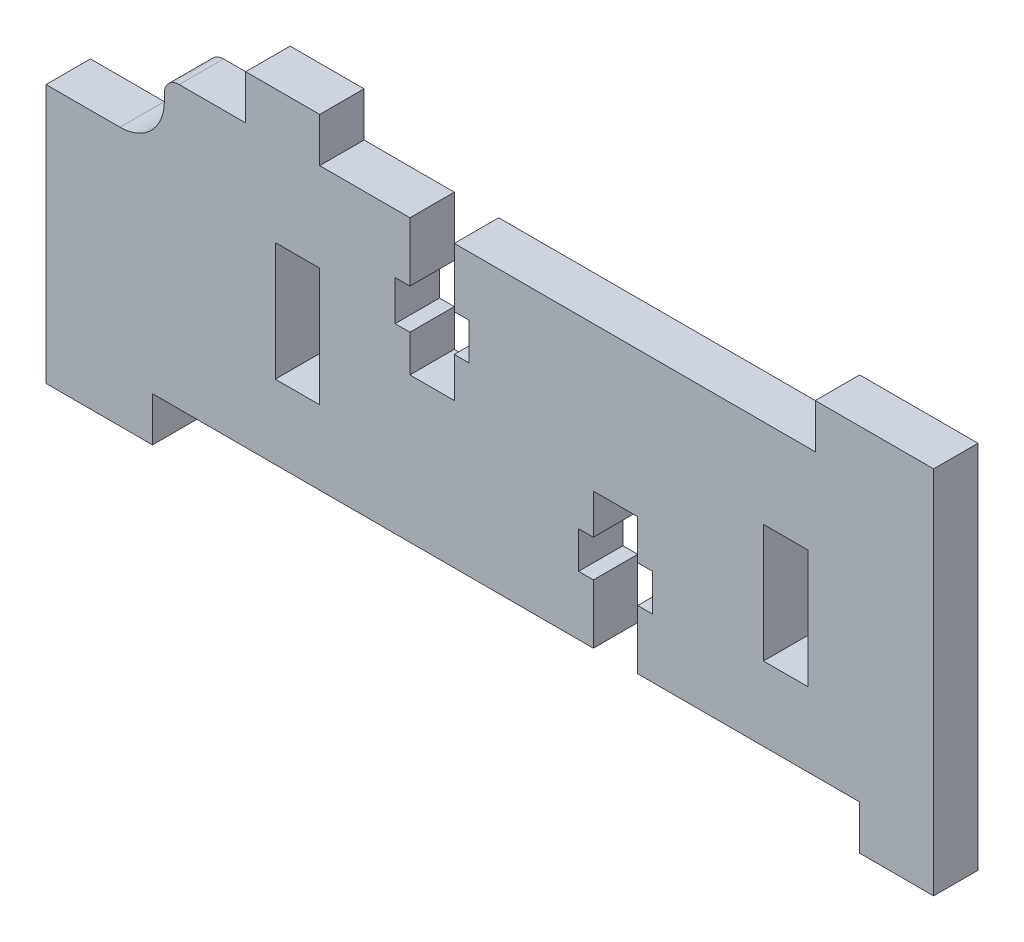
SolidWorks part; units mm, degrees
ref_plane "Plan de face" through (0, 0, 0) normal (0, 0, 1) x (1, 0, 0)
ref_plane "Plan de dessus" through (0, 0, 0) normal (0, 1, 0) x (1, 0, 0)
ref_plane "Plan de droite" through (0, 0, 0) normal (1, 0, 0) x (0, 0, -1)
sketch "Esquisse1" plane through (0, 0, 0) normal (0, 0, 1) x (1, 0, 0)
  line L0 (-0.0591, 12.771) -> (59.9317, 13.8182) construction
  line L1 (0, 0) -> (60, 0) construction
  line L2 (0, 0) -> (0, 25) construction
  line L3 (0, 25) -> (60, 25) construction
  line L4 (60, 0) -> (60, 25) construction
  line L5 (60, 25) -> (60, 0)
  line L6 (60, 0) -> (55, 0)
  line L7 (55, 0) -> (55, 3)
  line L8 (55, 3) -> (40, 3)
  line L9 (40, 3) -> (40, 7)
  line L10 (40, 7) -> (41, 7)
  line L11 (41, 7) -> (41, 9.5)
  line L12 (41, 9.5) -> (40, 9.5)
  line L13 (40, 9.5) -> (40, 12.2)
  line L14 (40, 12.2) -> (37, 12.2)
  line L15 (37, 12.2) -> (37, 9.5)
  line L16 (37, 9.5) -> (36, 9.5)
  line L17 (36, 9.5) -> (36, 7)
  line L18 (36, 7) -> (37, 7)
  line L19 (37, 7) -> (37, 3)
  line L20 (37, 3) -> (7.2, 3)
  line L21 (7.2, 3) -> (7.2, 0)
  line L22 (7.2, 0) -> (0, 0)
  line L23 (0, 0) -> (0, 17.5)
  line L24 (0, 17.5) -> (5, 17.5)
  line L25 (8, 20.5) -> (8, 22)
  line L26 (8, 22) -> (13.5, 22)
  line L27 (13.5, 22) -> (13.5, 25)
  line L28 (13.5, 25) -> (18.5, 25)
  line L29 (18.5, 25) -> (18.5, 22)
  line L30 (18.5, 22) -> (24.6, 22)
  line L31 (24.6, 22) -> (24.6, 18)
  line L32 (24.6, 18) -> (23.6, 18)
  line L33 (23.6, 18) -> (23.6, 15.3)
  line L34 (23.6, 15.3) -> (24.6, 15.3)
  line L35 (24.6, 15.3) -> (24.6, 12.8)
  line L36 (24.6, 12.8) -> (27.6, 12.8)
  line L37 (27.6, 12.8) -> (27.6, 15.5)
  line L38 (27.6, 15.5) -> (28.6, 15.5)
  line L39 (28.6, 15.5) -> (28.6, 18)
  line L40 (28.6, 18) -> (27.6, 18)
  line L41 (27.6, 18) -> (27.6, 22)
  line L42 (27.6, 22) -> (52, 22)
  line L43 (52, 22) -> (52, 25)
  line L44 (52, 25) -> (60, 25)
  line L45 (27.6, 12.8) -> (27.6, 22) construction
  line L46 (15.5, 16) -> (18.5, 16)
  line L47 (15.5, 16) -> (15.5, 8)
  line L48 (15.5, 8) -> (18.5, 8)
  line L49 (18.5, 16) -> (18.5, 8)
  line L50 (48.5, 16) -> (51.5, 16)
  line L51 (48.5, 16) -> (48.5, 8)
  line L52 (48.5, 8) -> (51.5, 8)
  line L53 (51.5, 16) -> (51.5, 8)
  line L54 (24.6, 22) -> (24.6, 12.8) construction
  line L55 (26.1, 12.8) -> (26.1, 22.7532) construction
  line L56 (18.5, 8) -> (48.5, 8) construction
  arc A0 (8, 20.5) -> (5, 17.5) centre (5, 20.5) cw
  point P52 (27.6, 20)
  point P55 (41, 8.25)
  point P58 (8, 17.5)
  dimension "D47" = 3
  dimension "D1" = 25
  dimension "D2" = 60
  dimension "D3" = 60
  dimension "D4" = 8
  dimension "D5" = 3
  dimension "D6" = 33.5
  dimension "D7" = 3
  dimension "D8" = 3
  dimension "D9" = 32.4
  dimension "D10" = 9.2
  dimension "D11" = 3
  dimension "D12" = 4
  dimension "D13" = 4
  dimension "D14" = 5
  dimension "D15" = 2.5
  dimension "D16" = 2.5
  dimension "D17" = 5
  dimension "D18" = 3
  dimension "D19" = 3
  dimension "D20" = 20
  dimension "D21" = 3
  dimension "D22" = 9.2
  dimension "D23" = 19
  dimension "D24" = 5
  dimension "D25" = 1
  dimension "D26" = 4
  dimension "D27" = 4
  dimension "D28" = 3
  dimension "D29" = 1
  dimension "D30" = 2.5
  dimension "D31" = 2.5
  dimension "D32" = 8.5
  dimension "D33" = 8
  dimension "D34" = 6
  dimension "D35" = 5
  dimension "D36" = 3
  dimension "D37" = 30
  dimension "D38" = 3
  dimension "D39" = 3
  dimension "D40" = 8
  dimension "D41" = 5
  dimension "D42" = 7.2
  dimension "D43" = 8
  dimension "D44" = 19
  dimension "D45" = 5
  dimension "D46" = 17.5
base flange "Tôle de base pliée1" sketch "Esquisse1" thickness 3 reverse thickness direction no parameters "D1"=1.5
fillet "Congé1" radius 1 1 edges at (8, 22, -1.5)
sketch "Lignes de pliage1" [suppressed] plane through (0, 0, 0) normal (0, 1, 0) x (1, 0, 0)
sketch "Cube de visualisation1" [suppressed] plane through (0, 0, 0) normal (0, 1, 0) x (1, 0, 0)
sheet metal parameters "Tôlerie1" thickness 3 parameters "D1"=1.5
flat pattern "Etat déplié1" [suppressed]
sketch "Lignes de pliage2" plane through (0, 0, 0) normal (0, 1, 0) x (1, 0, 0)
sketch3d "Cube de visualisation2" [suppressed]
  line L0 (-5, -20.5, 0) -> (55, -20.5, 0) construction
  line L1 (-5, 4.5, 0) -> (55, 4.5, 0) construction
  line L2 (-5, -20.5, 0) -> (-5, 4.5, 0) construction
  line L3 (55, -20.5, 0) -> (55, 4.5, 0) construction
